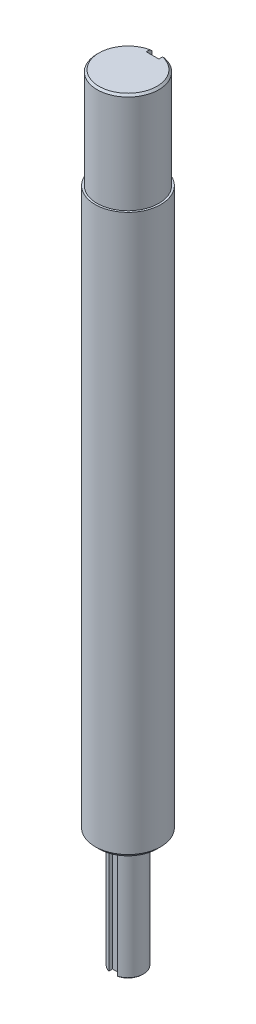
SolidWorks part; units mm, degrees
ref_plane "Front Plane" through (0, 0, 0) normal (0, 0, 1) x (1, 0, 0)
ref_plane "Top Plane" through (0, 0, 0) normal (0, 1, 0) x (1, 0, 0)
ref_plane "Right Plane" through (0, 0, 0) normal (1, 0, 0) x (0, 0, -1)
sketch "Sketch1" plane through (0, 0, 0) normal (0, 0, 1) x (1, 0, 0)
  line L1 (8.5, 201) -> (0, 201)
  line L2 (8.5, 201) -> (8.5, 0)
  line L3 (8.5, 0) -> (0, 0)
  line L4 (0, 201) -> (0, 0)
  line L5 (8.5, 201) -> (0, 0) construction
  line L6 (8.5, 0) -> (0, 201) construction
  point P0 (4.25, 100.5)
  dimension "D1" = 8.5
  dimension "D2" = 201
revolve "Revolve1" add sketch "Sketch1" angle 360 about L4
ref_axis "Axis1" through (0, 0, 0) along (0, 1, 0)
sketch "Sketch2" plane through (0, 201, 0) normal (0, 1, 0) x (1, 0, 0)
  circle A0 centre (0, 0) radius 8
  dimension "D1" = 16
extrude "Cut-Extrude1" cut sketch "Sketch2" against normal blind 26 flip side to cut
sketch "Sketch3" plane through (0, 201, 0) normal (0, 1, 0) x (1, 0, 0)
  line L1 (-1.625, 9.625) -> (1.625, 9.625)
  line L2 (-1.625, 9.625) -> (-1.625, 6.375)
  line L3 (-1.625, 6.375) -> (1.625, 6.375)
  line L4 (1.625, 9.625) -> (1.625, 6.375)
  line L5 (-1.625, 9.625) -> (1.625, 6.375) construction
  line L6 (-1.625, 6.375) -> (1.625, 9.625) construction
  circle A0 centre (0, 0) radius 8 construction
  point P0 (0, 8)
  point P7 (0, 0)
  dimension "D1" = 3.25
extrude "Cut-Extrude2" cut sketch "Sketch3" against normal up to surface (26 mm away) up to face at (-8, 175, 0)
chamfer "Chamfer1" distance 0.5 angle 45 2 edges at (-8.5, 0, 0) (0, 201, 8)
sketch "Sketch4" plane through (0, 0, 0) normal (0, -1, 0) x (1, 0, 0)
  circle A0 centre (0, 0) radius 4
  dimension "D1" = 8
extrude "Cut-Extrude3" cut sketch "Sketch4" against normal blind 30 flip side to cut
chamfer "Chamfer2" distance 1 angle 45 1 edges at (8.5, 30, 0)
sketch "Sketch5" plane through (0, 0, 0) normal (0, -1, 0) x (1, 0, 0)
  line L1 (-1.125, 5.125) -> (1.125, 5.125)
  line L2 (-1.125, 5.125) -> (-1.125, 2.875)
  line L3 (-1.125, 2.875) -> (1.125, 2.875)
  line L4 (1.125, 5.125) -> (1.125, 2.875)
  line L5 (-1.125, 5.125) -> (1.125, 2.875) construction
  line L6 (-1.125, 2.875) -> (1.125, 5.125) construction
  circle A1 centre (0, 0) radius 4 construction
  circle A2 centre (0, 0) radius 4 construction
  point P0 (0, 4)
  point P9 (0, 0)
  point P11 (0, 0)
  dimension "D1" = 2.25
extrude "Cut-Extrude4" cut sketch "Sketch5" against normal up to surface (30 mm away) up to face at (7.5, 30, 0)
chamfer "Chamfer3" distance 0.2 angle 45 4 edges at (-1.125, 0, 3.3568) (0, 0, 2.875) (1.125, 0, 3.3568) (0, 0, -4)
